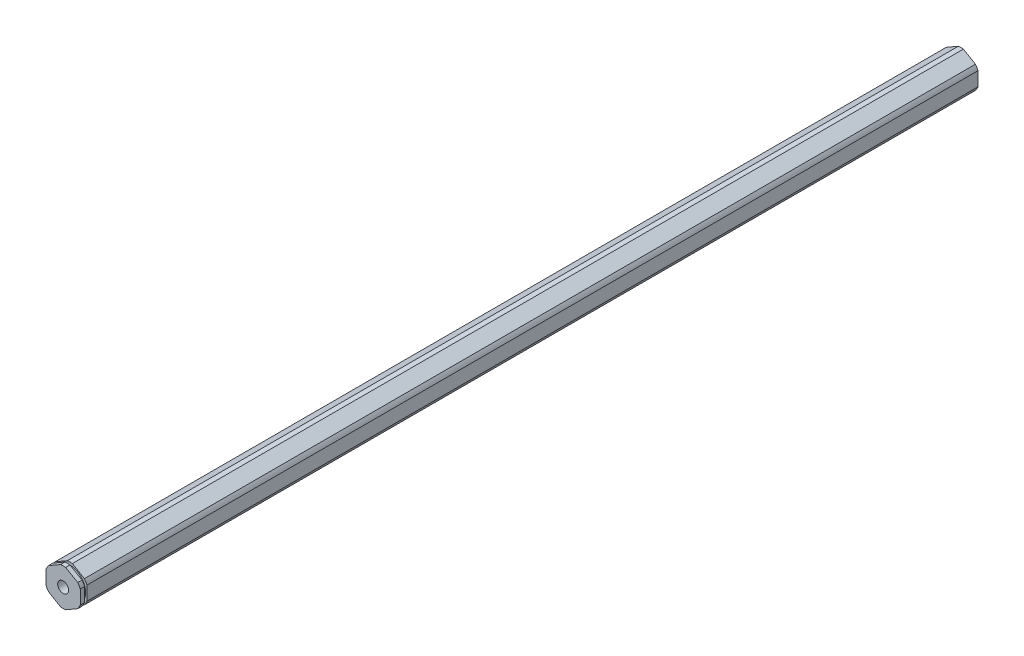
SolidWorks part; units mm, degrees
ref_plane "Front Plane" through (0, 0, 0) normal (0, 0, 1) x (1, 0, 0)
ref_plane "Top Plane" through (0, 0, 0) normal (0, 1, 0) x (1, 0, 0)
ref_plane "Right Plane" through (0, 0, 0) normal (1, 0, 0) x (0, 0, -1)
sketch "Sketch1" plane through (0, 0, 0) normal (0, 0, 1) x (1, 0, 0)
  line L1 (0, 7.3323) -> (-6.35, 3.6662)
  line L2 (-6.35, 3.6662) -> (-6.35, -3.6662)
  line L3 (-6.35, -3.6662) -> (0, -7.3323)
  line L4 (0, -7.3323) -> (6.35, -3.6662)
  line L5 (6.35, -3.6662) -> (6.35, 3.6662)
  line L6 (6.35, 3.6662) -> (0, 7.3323)
  circle A0 centre (0, 0) radius 6.35 construction
  circle A1 centre (0, 0) radius 6.858
  dimension "D1" = 12.7
  dimension "D2" = 13.716
extrude "Boss-Extrude1" add sketch "Sketch1" along normal mid plane 332.6765 contours L5 A1 L6 L1 L2 L3 L4 region at (0, 0, 0)
hole_wizard "#10-32 Tapped Hole1" positions "3DSketch1" profile "Sketch2" tap size "#10-32" standard "ANSI Inch"
sketch3d "3DSketch1"
  line L0 (0, 0, 166.3382) -> (0, 0, -166.3382) construction
  line L1 (0, 0, 166.3382) -> (0, 0, -166.3382) construction
  point P0 (0, 0, 166.3382)
  point P4 (0, 0, -166.3382)
sketch "Sketch2" plane through (0, 0, 166.3382) normal (1, 0, 0) x (0, -1, 0)
  line L0 (0, 0) -> (0, 17.5608)
  line L1 (0, 17.5608) -> (2.0193, 16.3474)
  line L2 (2.0193, 16.3474) -> (2.0193, 0)
  line L5 (2.0193, 0) -> (0, 0)
  line L10 (0, 17.5608) -> (-2.0193, 16.3474) construction
  line L11 (0, -6.35) -> (0, 107.95) construction
  dimension "Tap Drill Dia." = 4.0386
  dimension "Tap Drill Depth" = 16.3474
  dimension "Drill Angle" = 118
cosmetic thread "Hole Thread1" parameters "D1"=13.97, "D2"=4.826
cosmetic thread "Hole Thread2" parameters "D1"=13.97, "D2"=4.826
sketch "Sketch5" plane through (0, 0, 0) normal (1, 0, 0) x (0, 0, -1)
  line L0 (166.3382, 6.858) -> (-166.3382, 6.858) construction
  line L1 (-164.7507, 6.858) -> (-163.8618, 6.858)
  line L2 (-164.7507, 6.858) -> (-164.7508, 5.8547)
  line L3 (-164.7508, 5.8547) -> (-163.8618, 5.8547)
  line L4 (-163.8618, 6.858) -> (-163.8618, 5.8547)
  line L5 (-165.0472, 0) -> (-158.8423, 0) construction
  dimension "D1" = 5.8547
  dimension "D2" = 0.889
  dimension "D3" = 1.5875
revolve "Cut-Revolve1" cut sketch "Sketch5" angle 360 about L5
mirror "Mirror1" [suppressed] about plane through (0, 0, 0) normal (0, 0, 1)
